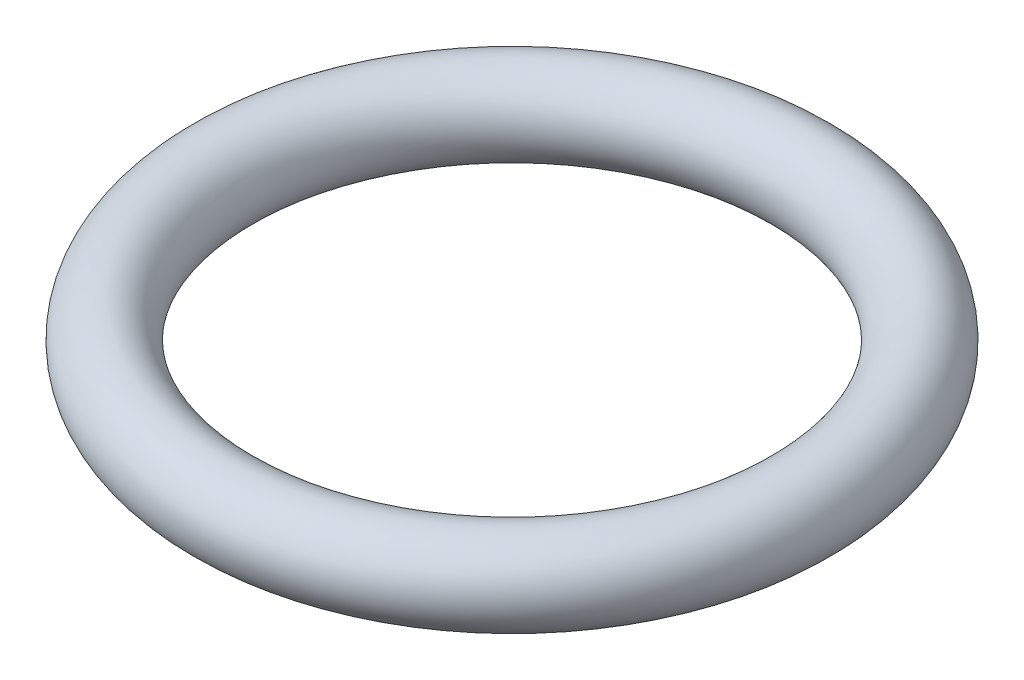
SolidWorks part; units mm, degrees
ref_plane "Face" through (0, 0, 0) normal (0, 0, 1) x (1, 0, 0)
ref_plane "Dessus" through (0, 0, 0) normal (0, 1, 0) x (1, 0, 0)
ref_plane "Droite" through (0, 0, 0) normal (1, 0, 0) x (0, 0, -1)
sketch "Esquisse1" plane through (0, 0, 0) normal (0, 0, 1) x (1, 0, 0)
  line L0 (0, 22.9367) -> (0, -22.9367) construction
  circle A0 centre (3.5, 0) radius 0.5
  dimension "D1" = 1
  dimension "D2" = 7
revolve "Base-Révolution" add sketch "Esquisse1" angle 360 about L0
ref_axis "Axe1" through (0, 0.525, 0) along (0, -1, 0)
